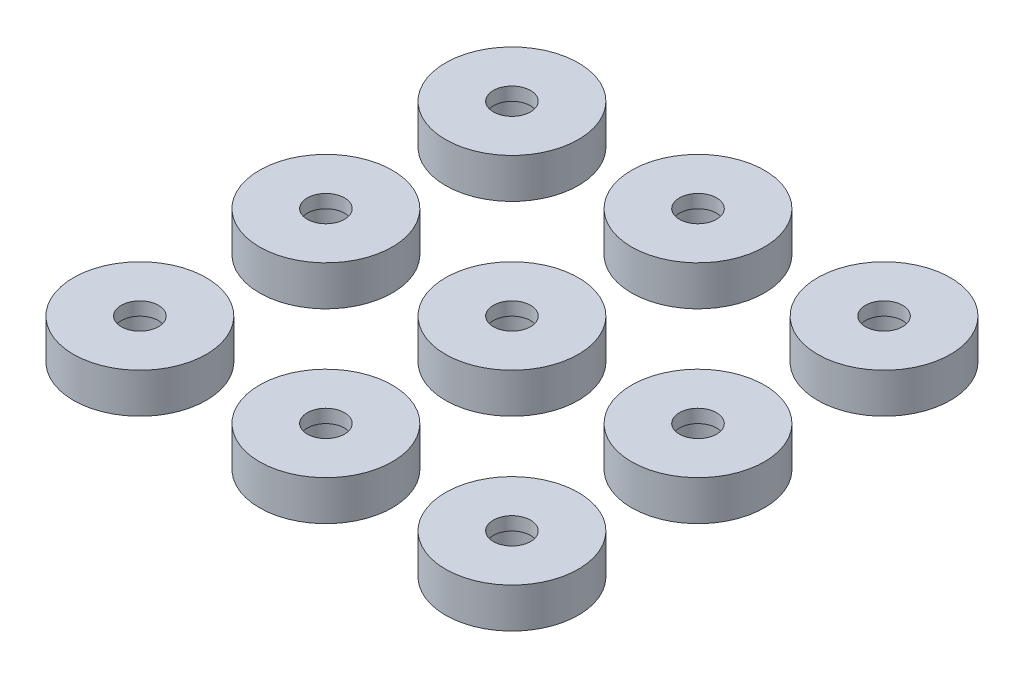
SolidWorks part; units mm, degrees
ref_plane "前视基准面" through (0, 0, 0) normal (0, 0, 1) x (1, 0, 0)
ref_plane "上视基准面" through (0, 0, 0) normal (0, 1, 0) x (1, 0, 0)
ref_plane "右视基准面" through (0, 0, 0) normal (1, 0, 0) x (0, 0, -1)
other "Configuration Table"
sketch "草图1" plane through (0, 0, 0) normal (0, 1, 0) x (1, 0, 0)
  circle A0 centre (0, 0) radius 2.5
  circle A1 centre (0, 0) radius 0.7
  circle A2 centre (0, 0) radius 1
  dimension "D1" = 1.4
  dimension "D2" = 2
  dimension "D3" = 5
extrude "凸台-拉伸1" add sketch "草图1" along normal blind 1.5 contours A0
extrude "切除-拉伸2" cut sketch "草图1<5>" along normal blind 1 contours A2
sketch "草图1<5>" plane through (0, 0, 0) normal (0, 1, 0) x (1, 0, 0) same geometry as "草图1"
extrude "切除-拉伸3" cut sketch "草图1<6>" along normal through all contours A1 region at (0, 0, 0)
sketch "草图1<6>" plane through (0, 0, 0) normal (0, 1, 0) x (1, 0, 0) same geometry as "草图1"
ref_plane "基准面1" through (0, 0, 3) normal (0, 0, 1) x (1, 0, 0)
pattern_linear "阵列(线性)1" count 3 spacing 7 along (0, 0, 1) of bodies 108
ref_plane "基准面2" through (3, 0, 0) normal (1, 0, 0) x (0, 0, -1)
pattern_linear "阵列(线性)2" count 3 spacing 7 along (1, 0, 0) of bodies 108 109 110
